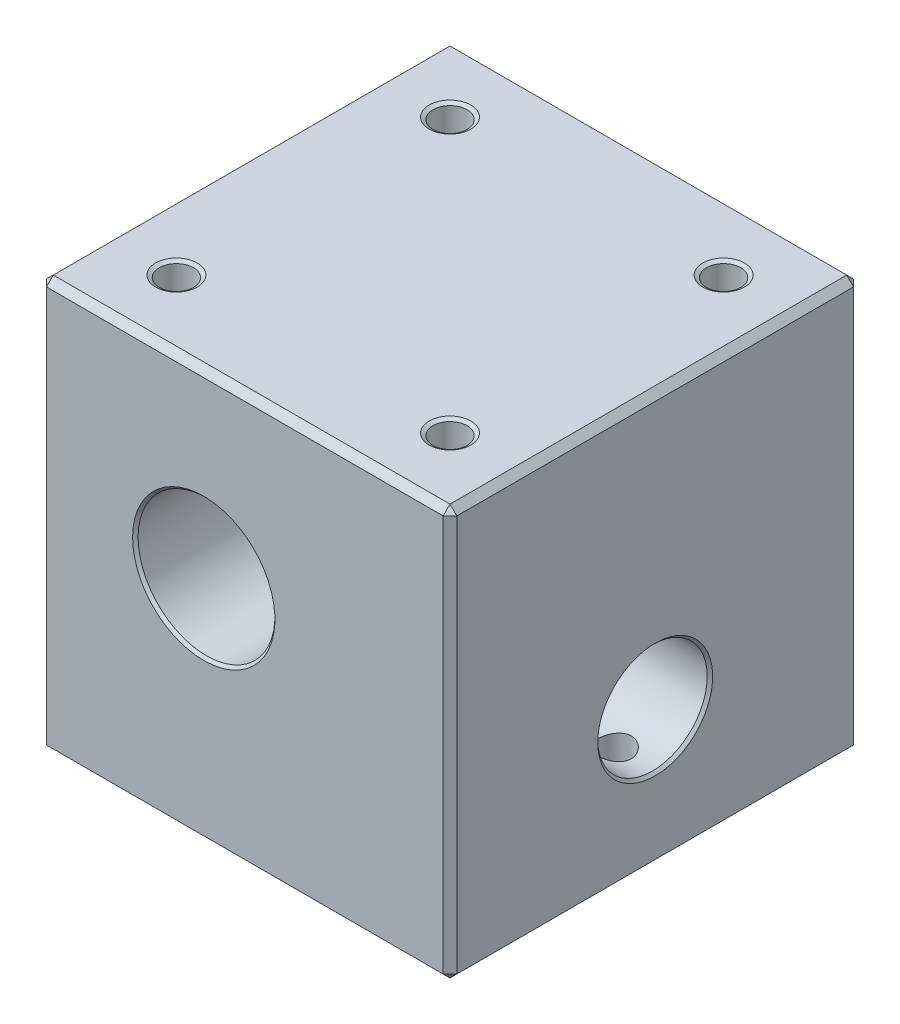
SolidWorks part; units mm, degrees
material "6063-T5"
ref_plane "Piano frontale" through (0, 0, 0) normal (0, 0, 1) x (1, 0, 0)
ref_plane "Piano superiore" through (0, 0, 0) normal (0, 1, 0) x (1, 0, 0)
ref_plane "Piano destro" through (0, 0, 0) normal (1, 0, 0) x (0, 0, -1)
sketch "Schizzo1" plane through (0, 0, 0) normal (0, 0, 1) x (1, 0, 0)
  line L0 (12, 6.5764) -> (12, 28.444) construction
  line L1 (0, 0) -> (30, 0)
  line L2 (0, 0) -> (0, 30)
  line L3 (0, 30) -> (30, 30)
  line L4 (30, 0) -> (30, 30)
  line L5 (6.315, 16.8) -> (24.6155, 16.8) construction
  circle A0 centre (12, 16.8) radius 5
  dimension "D3" = 10
  dimension "D1" = 30
  dimension "D2" = 30
  dimension "D4" = 12
  dimension "D5" = 13.2
extrude "Estrusione-Estrusione1" add sketch "Schizzo1" along normal blind 30
sketch "Schizzo3" plane through (30, 0, 0) normal (1, 0, 0) x (0, 0, -1)
  line L2 (-15, 10.16) -> (-15, 24.3684) construction
  line L3 (-30, 0) -> (-30, 30) construction
  line L4 (0, 0) -> (0, 30) construction
  line L5 (-30, 0) -> (0, 0) construction
  point P0 (-15, 10)
  dimension "D1" = 10
hole_wizard "Ø8.0 (8) Diameter Hole1" positions "Schizzo5" profile "Schizzo4" hole size "Ø8.0" standard "ISO"
sketch "Schizzo5" plane through (30, 0, 0) normal (1, 0, 0) x (0, 0, -1)
  point P0 (-15, 10)
sketch "Schizzo4" plane through (30, 10, 15) normal (0, 1, 0) x (0, 0, -1)
  line L0 (0, 0) -> (0, 15.9034)
  line L1 (0, 15.9034) -> (4, 13.5)
  line L2 (4, 13.5) -> (4, 0)
  line L5 (4, 0) -> (0, 0)
  line L10 (0, 15.9034) -> (-4, 13.5) construction
  line L11 (0, -6.35) -> (0, 107.95) construction
  dimension "Hole Dia." = 8
  dimension "Hole Depth" = 13.5
  dimension "Drill Angle" = 118
sketch "Schizzo6" plane through (0, 30, 0) normal (0, 1, 0) x (1, 0, 0)
  line L0 (-7.6843, -25) -> (41.504, -25) construction
  line L1 (0, -30) -> (0, 0) construction
  line L2 (30, -30) -> (0, -30) construction
  point P0 (5, -25)
  point P1 (25, -25)
  dimension "D1" = 20
  dimension "D2" = 5
  dimension "D3" = 5
hole_wizard "Foro filettato M3-1" positions "Schizzo8" profile "Schizzo7" tap size "M3" standard "ISO"
sketch "Schizzo8" plane through (0, 30, 0) normal (0, 1, 0) x (1, 0, 0)
  point P0 (5, -25)
  point P3 (25, -25)
sketch "Schizzo7" plane through (5, 30, 25) normal (1, 0, 0) x (0, 0, 1)
  line L0 (0, 0) -> (0, 9.2511)
  line L1 (0, 9.2511) -> (1.25, 8.5)
  line L2 (1.25, 8.5) -> (1.25, 0.1588)
  line L3 (1.25, 0.1588) -> (1.525, 0)
  line L5 (1.525, 0) -> (0, 0)
  line L6 (-1.25, 0.1588) -> (-1.525, 0) construction
  line L10 (0, 9.2511) -> (-1.25, 8.5) construction
  line L11 (0, -6.35) -> (0, 107.95) construction
  dimension "Tap Drill Dia." = 2.5
  dimension "Tap Drill Depth" = 8.5
  dimension "Near C'Sink Dia." = 3.05
  dimension "Near C'Sink Angle" = 120
  dimension "Drill Angle" = 118
cosmetic thread "Filettatura del foro1" parameters "D1"=6, "D2"=3
cosmetic thread "Filettatura del foro2" parameters "D1"=6, "D2"=3
ref_plane "Piano1" through (0, 0, 15) normal (0, 0, 1) x (1, 0, 0)
mirror "Specchia1" about plane through (0, 0, 15) normal (0, 0, 1) of "Foro filettato M3-1"
hole_wizard "Foro filettato M3-2" positions "Schizzo10" profile "Schizzo11" tap size "M3" standard "ISO"
sketch "Schizzo10" plane through (0, 0, 0) normal (0, -1, 0) x (-1, 0, 0)
  line L1 (-30, -30) -> (-30, 0) construction
  line L2 (-30, -15) -> (0, -15) construction
  line L3 (0, -30) -> (0, 0) construction
  point P0 (-27, -15)
  dimension "D2" = 3
sketch "Schizzo11" plane through (27, 0, 15) normal (1, 0, 0) x (0, 0, -1)
  line L0 (0, 0) -> (0, 9.2511)
  line L1 (0, 9.2511) -> (1.25, 8.5)
  line L2 (1.25, 8.5) -> (1.25, 0.1588)
  line L3 (1.25, 0.1588) -> (1.525, 0)
  line L5 (1.525, 0) -> (0, 0)
  line L6 (-1.25, 0.1588) -> (-1.525, 0) construction
  line L10 (0, 9.2511) -> (-1.25, 8.5) construction
  line L11 (0, -6.35) -> (0, 107.95) construction
  dimension "Tap Drill Dia." = 2.5
  dimension "Tap Drill Depth" = 8.5
  dimension "Near C'Sink Dia." = 3.05
  dimension "Near C'Sink Angle" = 120
  dimension "Drill Angle" = 118
chamfer "Chamfer1" distance 0.5 angle 45 12 edges at (30, 15, 0) (15, 0, 0) (0, 0, 15) (15, 0, 30) (30, 0, 15) (0, 15, 0) (0, 15, 30) (30, 15, 30) (15, 30, 0) (30, 30, 15) (0, 30, 15) (15, 30, 30)
chamfer "Chamfer2" distance 0.2 angle 45 3 edges at (17, 16.8, 0) (17, 16.8, 30) (30, 10, 11)
